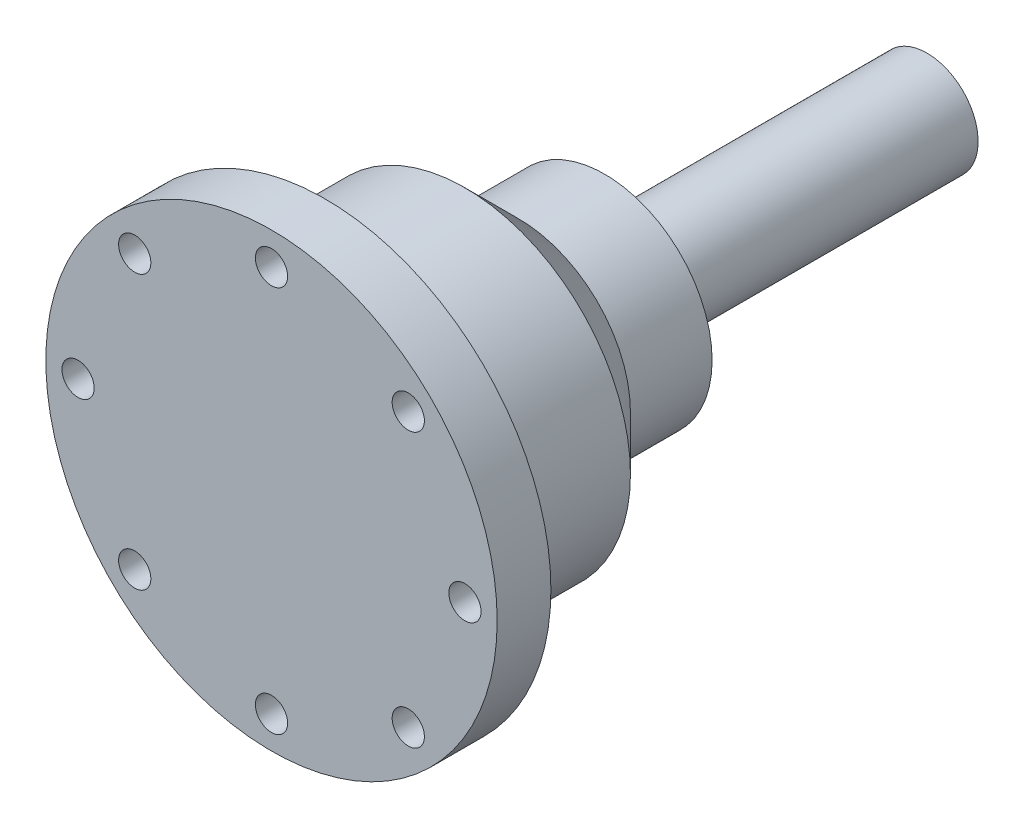
SolidWorks part; units mm, degrees
ref_plane "Front Plane" through (0, 0, 0) normal (0, 0, 1) x (1, 0, 0)
ref_plane "Top Plane" through (0, 0, 0) normal (0, 1, 0) x (1, 0, 0)
ref_plane "Right Plane" through (0, 0, 0) normal (1, 0, 0) x (0, 0, -1)
sketch "Sketch1" plane through (0, 0, 0) normal (0, 0, 1) x (1, 0, 0)
  circle A0 centre (0, 0) radius 10
  circle A1 centre (0, 0) radius 21
  circle A2 centre (0, 0) radius 15.4
  dimension "D1" = 20
  dimension "D2" = 42
  dimension "D3" = 30.8
extrude "Boss-Extrude1" add sketch "Sketch1" along normal blind 5 contours A0 | A2 A0 | A1 A2 region at (0, 0, 0) region at (-20.406, 0, 0) region at (-14.9644, 0, 0)
sketch "Sketch2" plane through (0, 0, 0) normal (0, 0, -1) x (-1, 0, 0)
  line L0 (0, 0) -> (0, 18) construction
  circle A0 centre (0, 18) radius 1.5
  dimension "D1" = 3
  dimension "D2" = 18
extrude "Cut-Extrude1" cut sketch "Sketch2" against normal through all
extrude "Boss-Extrude2" add sketch "Sketch1<3>" against normal blind 26 contours A0 region at (0, 0, 0)
sketch "Sketch1<3>" plane through (0, 0, 0) normal (0, 0, 1) x (1, 0, 0) same geometry as "Sketch1"
ref_axis "Axis1" through (0, 0, -26) along (0, 0, 1)
pattern_circular "CirPattern1" count 8 every 45 about axis through (0, 0, -26) along (0, 0, 1) of "Cut-Extrude1"
extrude "Boss-Extrude3" add sketch "Sketch1<4>" against normal blind 18 contours A2 A0 region at (-14.9644, 0, 0)
sketch "Sketch1<4>" plane through (0, 0, 0) normal (0, 0, 1) x (1, 0, 0) same geometry as "Sketch1"
chamfer "Chamfer2" distance 5 angle 45 1 edges at (15.4, 0, -18)
sketch "Sketch3" plane through (0, 0, -26) normal (0, 0, -1) x (-1, 0, 0)
  circle A0 centre (0, 0) radius 4.75
  dimension "D1" = 9.5
extrude "Boss-Extrude4" add sketch "Sketch3" along normal blind 30
